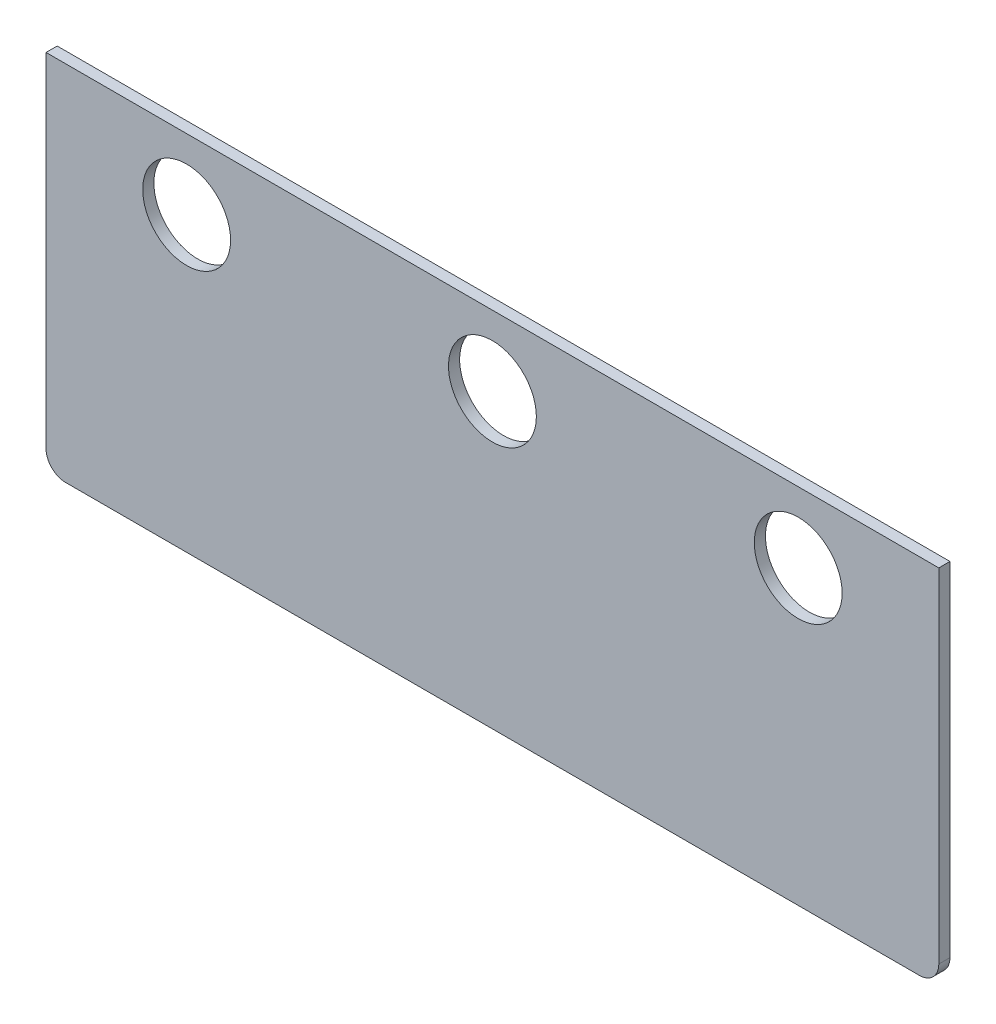
SolidWorks part; units mm, degrees
material "5052-H32"
ref_plane "Front Plane" through (0, 0, 0) normal (0, 0, 1) x (1, 0, 0)
ref_plane "Top Plane" through (0, 0, 0) normal (0, 1, 0) x (1, 0, 0)
ref_plane "Right Plane" through (0, 0, 0) normal (1, 0, 0) x (0, 0, -1)
sketch "Sketch1" plane through (0, 0, 0) normal (0, 0, 1) x (1, 0, 0)
  line L0 (-127, 103.175) -> (-127, 0)
  line L2 (127, 0) -> (127, 103.175)
  line L3 (127, 103.175) -> (-127, 103.175)
  line L4 (-127, 0) -> (127, 0)
  circle A0 centre (87, 83.175) radius 12.5
  circle A1 centre (-87, 83.175) radius 12.5
  circle A2 centre (0, 83.175) radius 12.5
  point P12 (0, 103.175)
  point P18 (0, 0)
  dimension "D4" = 25
  dimension "D1" = 103.175
  dimension "D2" = 254
  dimension "D3" = 20
  dimension "D5" = 40
  dimension "D6" = 40
extrude "Boss-Extrude1" add sketch "Sketch1" along normal blind 3.175
fillet "Fillet1" radius 5.5562 2 edges at (127, 0, 1.5875) (-127, 0, 1.5875)
equation "\"L\"= 420mm"
equation "\"W\"= 255mm"
equation "\"H\"= 110mm"
equation "\"Compartment Width\"= 80"
equation "\"T\"= 4.7625 * 2 / 3mm"
equation "\"Inside Fillet Radius\"= 5.55625mm"
equation "\"D1@Boss-Extrude1\"=\"T\""
equation "\"Hole\"=25mm"
equation "\"D4@Sketch1\"=\"Hole\""
equation "\"D2@Sketch1\"=\"W\"-1"
equation "\"D1@Sketch1\"=\"H\"+\"T\"-10"
equation "\"Offset\"= 18mm"
equation "\"Wheel to Wall\"= 43"
equation "\"D1@Fillet1\"=\"Inside Fillet Radius\""
